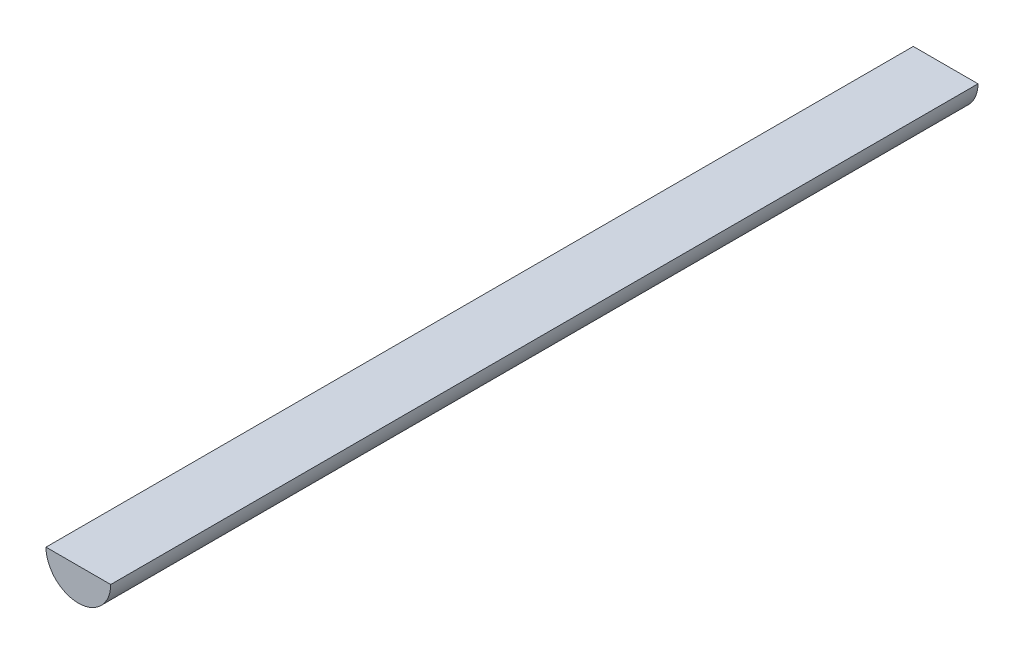
SolidWorks part; units mm, degrees
ref_plane "Front Plane" through (0, 0, 0) normal (0, 0, 1) x (1, 0, 0)
ref_plane "Top Plane" through (0, 0, 0) normal (0, 1, 0) x (1, 0, 0)
ref_plane "Right Plane" through (0, 0, 0) normal (1, 0, 0) x (0, 0, -1)
sketch "Sketch1" plane through (0, 0, 0) normal (0, 0, 1) x (1, 0, 0)
  line L0 (-15, 0) -> (15, 0)
  line L1 (-13.9642, -1) -> (13.9642, -1)
  arc A0 (-15, 0) -> (15, 0) centre (0, 0) ccw
  arc A1 (-13.9642, -1) -> (13.9642, -1) centre (0, 0) ccw
  dimension "D1" = 30
  dimension "D2" = 1
extrude "Boss-Extrude1" add sketch "Sketch1" along normal blind 400
sketch "Sketch2" plane through (0, 0, 400) normal (0, 0, 1) x (1, 0, 0)
  line L0 (15, 0) -> (-15, 0) construction
  line L1 (-15, 0) -> (15, 0)
  arc A0 (-15, 0) -> (15, 0) centre (0, 0) ccw
extrude "Boss-Extrude2" add sketch "Sketch2" along normal blind 1
sketch "Sketch3" plane through (0, 0, 0) normal (0, 0, -1) x (-1, 0, 0)
  line L0 (-15, 0) -> (15, 0)
  arc A0 (-15, 0) -> (15, 0) centre (0, 0) ccw
extrude "Boss-Extrude3" add sketch "Sketch3" along normal blind 1
